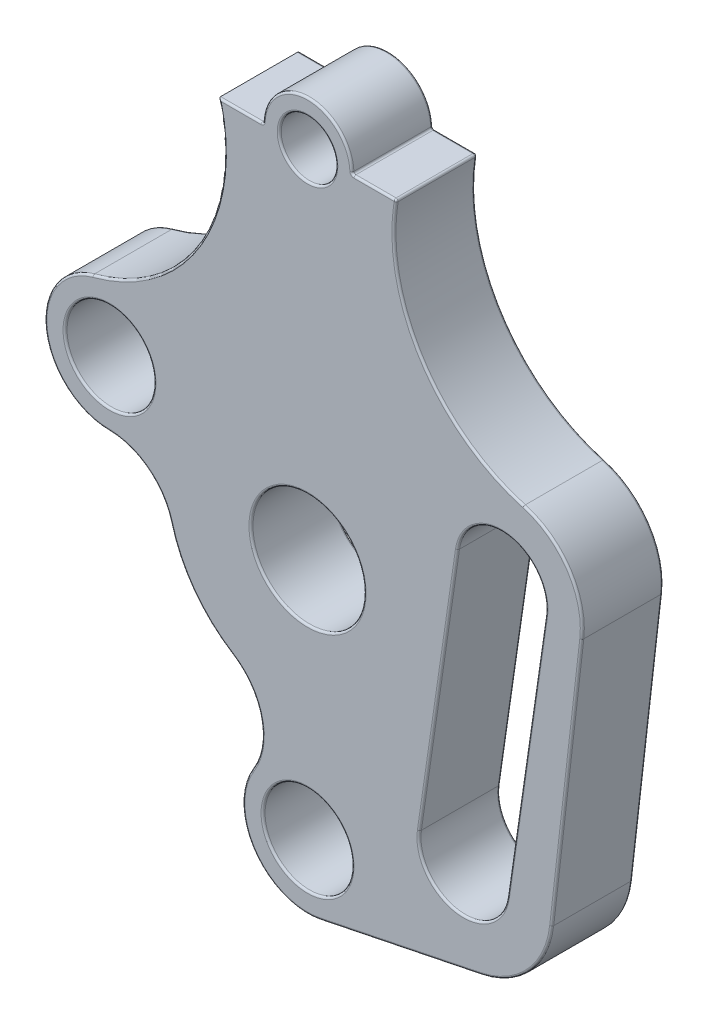
SolidWorks part; units mm, degrees
ref_plane "Front Plane" through (0, 0, 0) normal (0, 0, 1) x (1, 0, 0)
ref_plane "Top Plane" through (0, 0, 0) normal (0, 1, 0) x (1, 0, 0)
ref_plane "Right Plane" through (0, 0, 0) normal (1, 0, 0) x (0, 0, -1)
sketch "Sketch1" plane through (0, 0, 0) normal (0, 0, 1) x (1, 0, 0)
  line L0 (0, -1.6568) -> (0, 49998.3432) construction
  line L1 (11, 88) -> (22, 88)
  line L2 (-11, 88) -> (-22, 88)
  line L3 (4.8501, -5.7801) -> (32144.2306, -38308.0023) construction
  line L4 (67.8708, 16.7304) -> (60.4251, -48.4592)
  line L5 (42.9886, -67.5138) -> (3.2155, -75.6736)
  line L6 (58.8858, 17.4193) -> (49.4531, -47.5433)
  line L7 (37.1142, 20.5807) -> (27.4519, -45.9627)
  circle A0 centre (0, 0) radius 14
  arc A1 (11, 88) -> (-11, 88) centre (0, 88) ccw
  circle A2 centre (0, 88) radius 7
  circle A3 centre (0, -60) radius 11
  circle A4 centre (-49, 19) radius 11
  arc A5 (-13.5996, -51.5708) -> (3.2155, -75.6736) centre (0, -60) ccw
  arc A6 (-53.1566, 34.4507) -> (-49, 3) centre (-49, 19) ccw
  arc A7 (-22, 88) -> (-53.1566, 34.4507) centre (-64.5873, 76.9399) cw
  arc A8 (-33.8444, -8.9194) -> (-18.6661, -29.607) centre (0, 0) ccw
  arc A9 (-49, 3) -> (-33.8444, -8.9194) centre (-49.3161, -12.9969) cw
  arc A10 (-18.6661, -29.607) -> (-13.5996, -51.5708) centre (-27.1992, -43.1417) cw
  arc A11 (67.8708, 16.7304) -> (53.429, 38.2491) centre (48, 19) ccw
  arc A13 (22, 88) -> (53.429, 38.2491) centre (65.3727, 80.597) ccw
  arc A14 (58.1538, 14.7692) -> (37.1142, 20.5807) centre (48, 19) ccw
  arc A15 (27.6814, -44.382) -> (49.4531, -47.5433) centre (38.5673, -45.9627) ccw
  circle A16 centre (0, 0) radius 60 construction
  arc A17 (52.542, -28.9713) -> (52.1909, -28.6885) centre (38.5673, -45.9627) ccw
  arc A18 (42.9886, -67.5138) -> (60.4251, -48.4592) centre (38.5673, -45.9627) ccw
  point P41 (0, 0)
  point P44 (0, 0)
  point P45 (13.688, 84.638)
  point P46 (0, 0)
  dimension "D1" = 28
  dimension "D2" = 22
  dimension "D3" = 14
  dimension "D4" = 22
  dimension "D5" = 22
  dimension "D6" = 32
  dimension "D7" = 32
  dimension "D13" = 44
  dimension "D16" = 70
  dimension "D17" = 16
  dimension "D18" = 16
  dimension "D19" = 40
  dimension "D20" = 22
  dimension "D21" = 44
  dimension "D24" = 22
  dimension "D25" = 22
  dimension "D26" = 120
  dimension "D8" = 22
  dimension "D9" = 22
  dimension "D10" = 49
  dimension "D11" = 69
  dimension "D12" = 148
  dimension "D14" = 40
  dimension "D15" = 88
  dimension "D22" = 48
  dimension "D23" = 19
extrude "Boss-Extrude1" add sketch "Sketch1" along normal mid plane 20 contours L5 A18 L4 A11 A13 L1 A1 L2 A7 A6 A9 A8 A10 A5 A0 A2 A3 A4 A15 L7 A14 L6 region at (16.5, 85.802, 0)
fillet "Fillet1" radius 0.5 48 edges at (-16.5, 88, 10) (-26.5561, 54.8123, 10) (-26.5561, 54.8123, -10) (22, 88, 0) (11, 88, 0) (-11, 88, 0) (-49, 3, 0) (-13.1222, -69.1546, 10) (-11.6086, -39.5453, 10) (-28.2194, -20.7043, 10) (-39.4251, -0.4204, 10) (-64.8621, 16.9036, 10) (0, 99, 10) (16.5, 88, 10) (28.1737, 57.0974, 10) (64.6067, 30.1453, 10) (64.148, -15.8644, 10) (54.7975, -60.8146, 10) (23.1021, -71.5937, 10) (-38, 19, 10) (11, -60, 10) (7, 88, 10) (14, 0, 10) (49.5807, 29.8858, 10) (32.3978, -11.9007, 10) (36.9866, -56.8485, 10) (54.1695, -15.062, 10) (-13.1222, -69.1546, -10) (-11.6086, -39.5453, -10) (-28.2194, -20.7043, -10) (-39.4251, -0.4204, -10) (-64.8621, 16.9036, -10) (-16.5, 88, -10) (0, 99, -10) (16.5, 88, -10) (28.1737, 57.0974, -10) (64.6067, 30.1453, -10) (64.148, -15.8644, -10) (54.7975, -60.8146, -10) (23.1021, -71.5937, -10) (-38, 19, -10) (11, -60, -10) (7, 88, -10) (14, 0, -10) (49.5807, 29.8858, -10) (32.3978, -11.9007, -10) (36.9866, -56.8485, -10) (54.1695, -15.062, -10)
